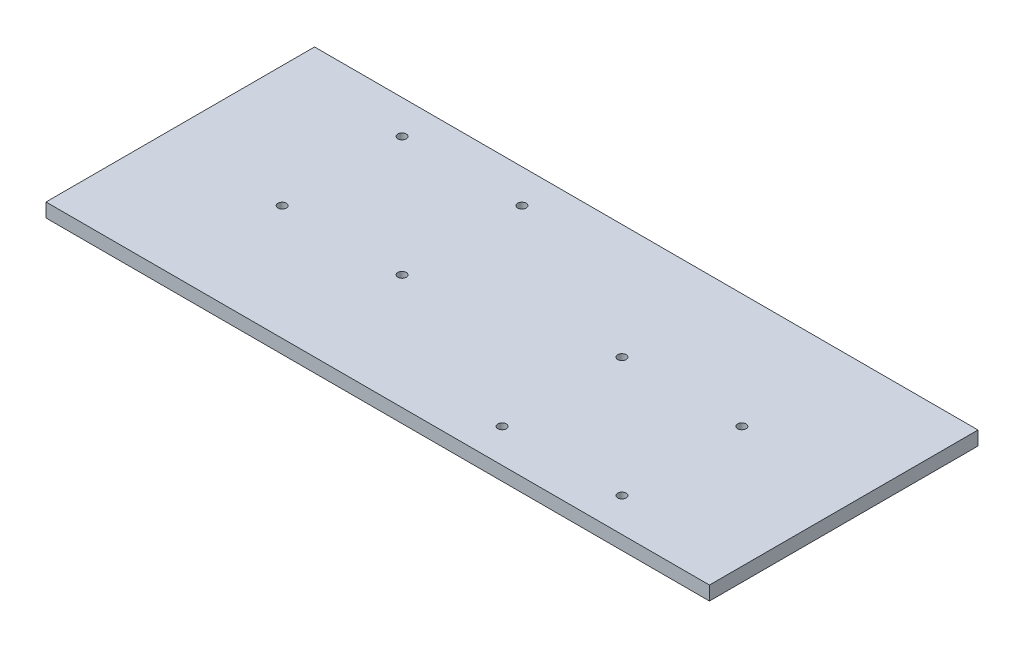
SolidWorks part; units mm, degrees
ref_plane "Front Plane" through (0, 0, 0) normal (0, 0, 1) x (1, 0, 0)
ref_plane "Top Plane" through (0, 0, 0) normal (0, 1, 0) x (1, 0, 0)
ref_plane "Right Plane" through (0, 0, 0) normal (1, 0, 0) x (0, 0, -1)
sketch "Sketch1" plane through (0, 0, 0) normal (0, 1, 0) x (1, 0, 0)
  line L1 (-133.35, -53.975) -> (133.35, -53.975)
  line L2 (-133.35, -53.975) -> (-133.35, 53.975)
  line L3 (-133.35, 53.975) -> (133.35, 53.975)
  line L4 (133.35, -53.975) -> (133.35, 53.975)
  line L5 (-133.35, -53.975) -> (133.35, 53.975) construction
  line L6 (-133.35, 53.975) -> (133.35, -53.975) construction
  point P0 (0, 0)
  dimension "D1" = 107.95
  dimension "D2" = 266.7
extrude "Boss-Extrude1" add sketch "Sketch1" along normal blind 5.588
sketch "Sketch2" plane through (0, 5.588, 0) normal (0, 1, 0) x (1, 0, 0)
  point P0 (-84.612, -7.775)
  point P1 (-84.612, 40.415)
  point P3 (-36.422, 40.415)
  point P5 (-36.422, -7.775)
  point P7 (84.612, -40.415)
  point P9 (84.612, 7.775)
  point P11 (36.422, 7.775)
  point P13 (36.422, -40.415)
hole_wizard "M3 Clearance Hole1" positions "Sketch3" profile "Sketch4" hole size "M3" standard "ANSI Metric" end condition through all
sketch "Sketch3" plane through (0, 5.588, 0) normal (0, 1, 0) x (1, 0, 0)
  point P0 (-84.612, -7.775)
  point P3 (-84.612, 40.415)
  point P6 (-36.422, 40.415)
  point P9 (-36.422, -7.775)
  point P12 (84.612, 7.775)
  point P15 (84.612, -40.415)
  point P18 (36.422, -40.415)
  point P21 (36.422, 7.775)
sketch "Sketch4" plane through (-84.612, 5.588, 7.775) normal (1, 0, 0) x (0, 0, 1)
  line L0 (0, 0) -> (0, 5.588)
  line L1 (0, 5.588) -> (1.7, 5.588)
  line L2 (1.7, 5.588) -> (1.7, 0)
  line L5 (1.7, 0) -> (0, 0)
  line L11 (0, -6.35) -> (0, 107.95) construction
  dimension "Thru Hole Dia." = 3.4
  dimension "Thru Hole Depth" = 5.588
